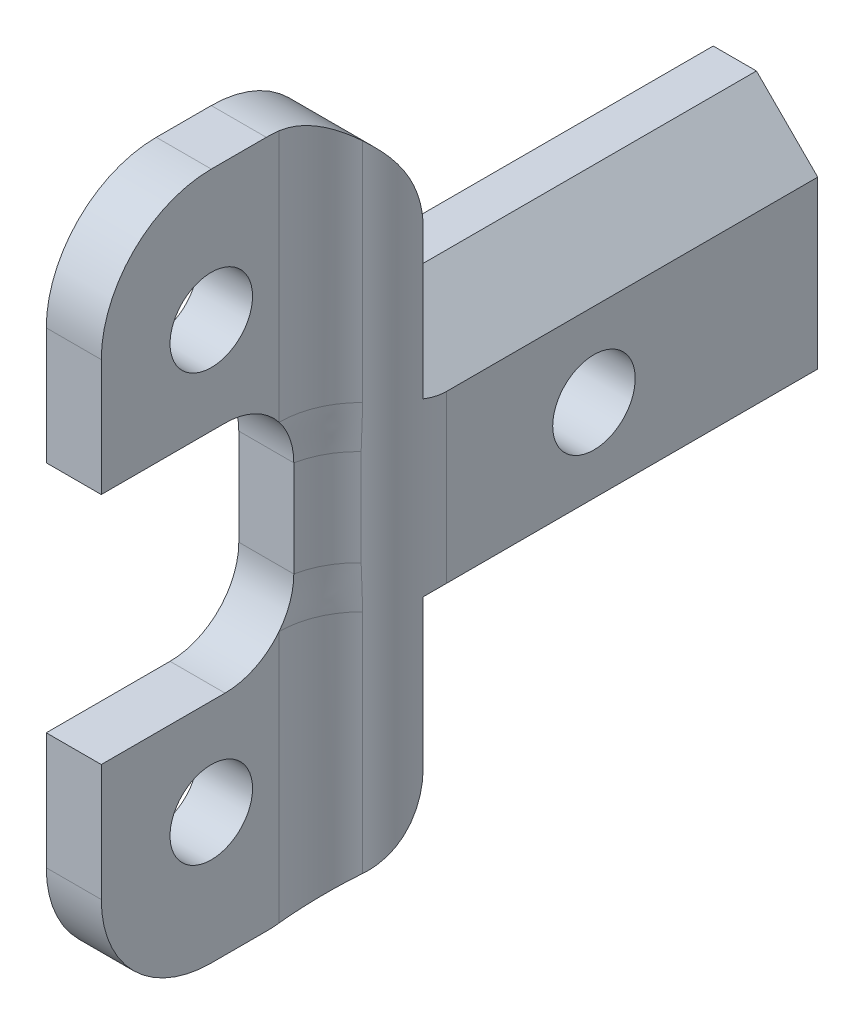
SolidWorks part; units mm, degrees
ref_plane "Front Plane" through (0, 0, 0) normal (0, 0, 1) x (1, 0, 0)
ref_plane "Top Plane" through (0, 0, 0) normal (0, 1, 0) x (1, 0, 0)
ref_plane "Right Plane" through (0, 0, 0) normal (1, 0, 0) x (0, 0, -1)
sketch "Sketch1" plane through (0, 0, 0) normal (0, 0, 1) x (1, 0, 0)
  line L0 (-23.672, 34.5) -> (-23.672, 36.875) construction
  line L1 (-23.672, 34.5) -> (-21.747, 34.5) construction
  line L2 (-23.672, 43.125) -> (-23.672, 45.5) construction
  line L3 (-23.672, 45.5) -> (-21.747, 45.5) construction
  line L4 (-21.747, 45.5) -> (-19.372, 43.125) construction
  line L5 (-19.372, 36.875) -> (-19.372, 43.125) construction
  line L6 (-21.747, 34.5) -> (-19.372, 36.875) construction
  line L7 (-23.672, 34.5) -> (-23.672, 36.875) construction
  line L8 (-23.672, 34.5) -> (-21.747, 34.5) construction
  line L9 (-23.672, 43.125) -> (-23.672, 45.5) construction
  line L10 (-23.672, 45.5) -> (-21.747, 45.5) construction
  line L11 (-21.747, 45.5) -> (-19.372, 43.125) construction
  line L12 (-19.372, 36.875) -> (-19.372, 43.125) construction
  line L13 (-21.747, 34.5) -> (-19.372, 36.875) construction
  line L14 (-23.422, 43.125) -> (-23.422, 45.25)
  line L15 (-23.422, 45.25) -> (-21.8506, 45.25)
  line L16 (-21.8506, 45.25) -> (-19.622, 43.0214)
  line L17 (-19.622, 36.9786) -> (-19.622, 43.0214)
  line L18 (-21.8506, 34.75) -> (-19.622, 36.9786)
  line L19 (-23.422, 34.75) -> (-21.8506, 34.75)
  line L20 (-23.422, 34.75) -> (-23.422, 43.125)
  line L21 (-23.422, 34.75) -> (-23.422, 36.875) construction
  dimension "D1" = 0.25
extrude "Boss-Extrude1" add sketch "Sketch1" against normal blind 14 and the other way blind 0.25
sketch "Sketch2" plane through (-23.422, 0, 0) normal (-1, 0, 0) x (0, 0, 1)
  circle A0 centre (-5.8636, 40) radius 1.5 construction
  circle A1 centre (-5.8636, 40) radius 1.5
extrude "Cut-Extrude1" cut sketch "Sketch2" against normal blind 14
sketch "Sketch3" plane through (0, 0, 0.25) normal (0, 0, 1) x (1, 0, 0)
  line L0 (-23.422, 45.25) -> (-23.422, 34.75) construction
  line L1 (-23.422, 52.5) -> (-19.622, 52.5)
  line L2 (-23.422, 52.5) -> (-23.422, 27.5)
  line L3 (-23.422, 27.5) -> (-19.622, 27.5)
  line L4 (-19.622, 52.5) -> (-19.622, 27.5)
  line L5 (-19.622, 36.9786) -> (-19.622, 43.0214) construction
  point P6 (-23.422, 40)
  point P7 (-23.422, 40)
  dimension "D1" = 25
extrude "Boss-Extrude2" add sketch "Sketch3" along normal blind 10
sketch "Sketch4" plane through (-23.422, 0, 0) normal (-1, 0, 0) x (0, 0, 1)
  line L0 (6.25, 47.75) -> (6.25, 32.25) construction
  line L1 (10.25, 52.5) -> (10.25, 27.5) construction
  line L2 (0.25, 52.5) -> (0.25, 45.25) construction
  line L3 (10.25, 44.25) -> (3.25, 44.25)
  line L4 (10.25, 44.25) -> (10.25, 35.75)
  line L5 (10.25, 35.75) -> (3.25, 35.75)
  line L6 (3.25, 44.25) -> (3.25, 35.75)
  circle A0 centre (6.25, 47.75) radius 1.5
  circle A1 centre (6.25, 32.25) radius 1.5
  point P6 (10.25, 40)
  point P7 (6.25, 40)
  dimension "D2" = 3
  dimension "D3" = 3
  dimension "D1" = 15.5
  dimension "D4" = 3.5
  dimension "D5" = 3.5
  dimension "D6" = 4
  dimension "D7" = 3
extrude "Cut-Extrude2" cut sketch "Sketch4" against normal through all and the other way through all
fillet "Fillet1" radius 4 4 edges at (-21.522, 52.5, 10.25) (-21.522, 27.5, 10.25) (-21.522, 27.5, 0.25) (-21.522, 52.5, 0.25)
fillet "Fillet2" radius 2.5 2 edges at (-21.522, 35.75, 3.25) (-21.522, 44.25, 3.25)
sketch "Sketch5" plane through (-19.622, 0, 0) normal (1, 0, 0) x (0, 0, -1)
  line L0 (-6.25, 27.5) -> (-4.25, 27.5) construction
  line L1 (-10.25, 52.5) -> (-2.25, 52.5)
  line L2 (-10.25, 52.5) -> (-10.25, 27.5)
  line L3 (-10.25, 27.5) -> (-2.25, 27.5)
  line L4 (-2.25, 52.5) -> (-2.25, 27.5)
  line L5 (-6.25, 52.5) -> (-4.25, 52.5) construction
  line L6 (-10.25, 44.25) -> (-10.25, 48.5) construction
  circle A0 centre (-6.25, 47.75) radius 1.5 construction
  dimension "D1" = 4
extrude "Cut-Extrude3" cut sketch "Sketch5" against normal offset from surface (1.8 mm away) 2 up to face at (-23.422, 32.25, 4.75)
fillet "Fillet3" radius 3 1 edges at (-19.622, 40, 2.25)
fillet "Fillet4" radius 3 1 edges at (-21.422, 40, 2.25)
equation "\"w\"=10"
